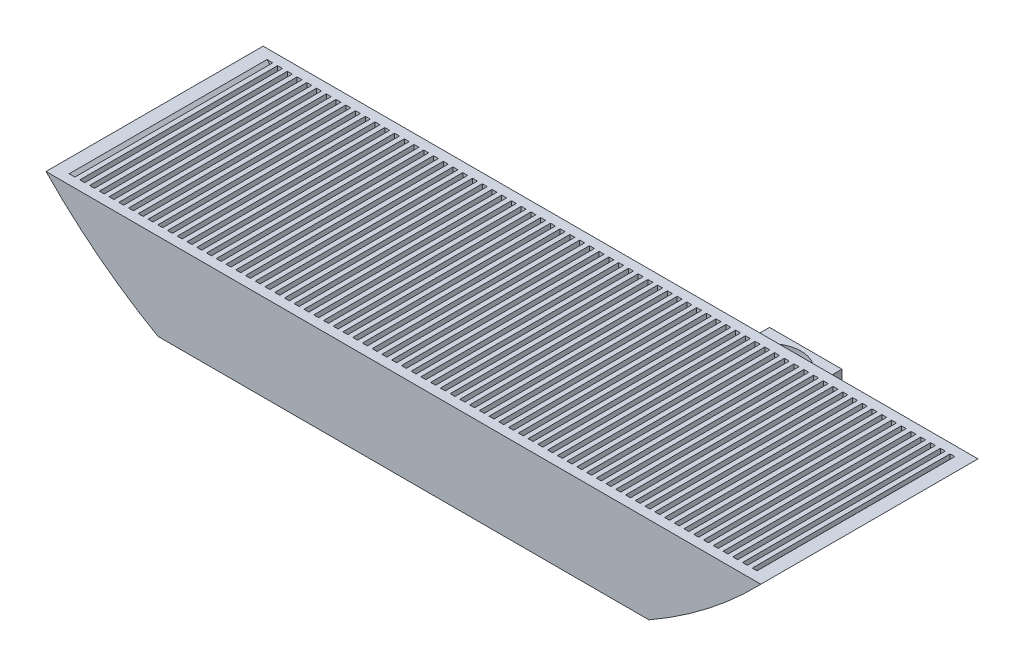
SolidWorks part; units mm, degrees
ref_plane "Plan de face" through (0, 0, 0) normal (0, 0, 1) x (1, 0, 0)
ref_plane "Plan de dessus" through (0, 0, 0) normal (0, 1, 0) x (1, 0, 0)
ref_plane "Plan de droite" through (0, 0, 0) normal (1, 0, 0) x (0, 0, -1)
sketch "Esquisse1" plane through (0, 0, 0) normal (0, 0, 1) x (1, 0, 0)
  line L0 (-50.3307, -8.3775) -> (51.4226, -8.3775)
  line L1 (74.6305, 9.6225) -> (31.2418, 9.6225)
  line L2 (31.2418, 9.6225) -> (12.2418, 9.6225)
  line L3 (12.2418, 9.6225) -> (-73.5385, 9.6225)
  arc A0 (51.4226, -8.3775) -> (74.6305, 9.6225) centre (0.546, 81.1802) ccw
  arc A1 (-73.5385, 9.6225) -> (-50.3307, -8.3775) centre (0.546, 81.1802) ccw
extrude "Boss.-Extru.1" add sketch "Esquisse1" along normal blind 45
shell "Coque1" thickness 2 removed face at (0.546, -8.3775, 22.5) removed face at (0.546, 9.6225, 22.5)
sketch "Esquisse2" plane through (0, 0, 2) normal (0, 0, 1) x (1, 0, 0)
  line L1 (-69.5385, 9.6225) -> (-68.5385, 9.6225)
  line L2 (-46.1491, -8.3775) -> (47.2411, -8.3775)
  line L3 (71.8237, 9.6225) -> (-70.7317, 9.6225)
  line L4 (-46.1491, -8.3775) -> (47.2411, -8.3775)
  line L5 (71.8237, 9.6225) -> (-69.5385, 9.6225)
  line L6 (-69.5385, 9.6225) -> (-69.5385, 7.6225)
  line L7 (-69.5385, 7.6225) -> (-68.5385, 7.6225)
  line L8 (-68.5385, 9.6225) -> (-68.5385, 7.6225)
  arc A2 (-70.7317, 9.6225) -> (-46.1491, -8.3775) centre (0.546, 81.1802) ccw
  arc A3 (47.2411, -8.3775) -> (71.8237, 9.6225) centre (0.546, 81.1802) ccw
  arc A5 (47.2411, -8.3775) -> (71.8237, 9.6225) centre (0.546, 81.1802) ccw
  point P10 (0, 0)
  arc M7 (-70.7317, 9.6225) -> (-46.1491, -8.3775) centre (0.546, 81.1802) ccw
  line M10 (71.8237, 9.6225) -> (-70.7317, 9.6225)
  dimension "D2" = 1
  dimension "D3" = 2
  dimension "D4" = 4
  dimension "D1" = 0
extrude "Boss.-Extru.4" add sketch "Esquisse2" along normal up to surface (41 mm away) contours L8 L6 L7 M10 M7 region at (-68.9923, 8.782, 2) up to face at (0.546, 0.1564, 43)
pattern_linear "Répétition linéaire1" count 70 spacing 2.02 along (1, 0, 0) of "Boss.-Extru.4"
sketch "Esquisse3" plane through (0, -8.3775, 0) normal (0, -1, 0) x (1, 0, 0)
  line L0 (-50.3307, 0) -> (51.4226, 0) construction
  line L1 (16.4226, 0) -> (31.4226, 0)
  line L2 (16.4226, 0) -> (16.4226, -15)
  line L3 (16.4226, -15) -> (31.4226, -15)
  line L4 (31.4226, 0) -> (31.4226, -15)
  line L5 (51.4226, 45) -> (51.4226, 0) construction
  circle A0 centre (23.9226, -7.5) radius 6.5
  dimension "D4" = 13
  dimension "D1" = 15
  dimension "D2" = 15
  dimension "D3" = 20
extrude "Boss.-Extru.5" add sketch "Esquisse3" against normal blind 5
fillet "Congé1" radius 0.25 3 edges at (31.4226, -5.8775, 0) (23.9226, -3.3775, 0) (16.4226, -5.8775, 0)
